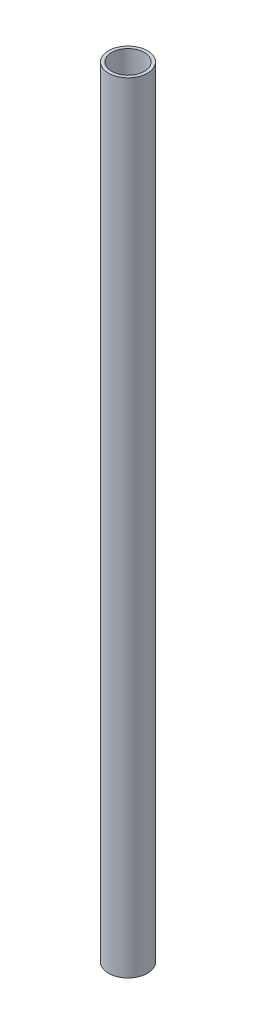
SolidWorks part; units mm, degrees
ref_plane "Front Plane" through (0, 0, 0) normal (0, 0, 1) x (1, 0, 0)
ref_plane "Top Plane" through (0, 0, 0) normal (0, 1, 0) x (1, 0, 0)
ref_plane "Right Plane" through (0, 0, 0) normal (1, 0, 0) x (0, 0, -1)
sketch "Sketch1" plane through (0, 0, 0) normal (0, 1, 0) x (1, 0, 0)
  circle A0 centre (0, 0) radius 12.5
  circle A1 centre (0, 0) radius 10.5
  dimension "D1" = 25
  dimension "D2" = 21
extrude "Boss-Extrude1" add sketch "Sketch1" along normal blind 500
equation "\"D1@Sketch1\" = \"cf_tube_outer_diameter\""
equation "\"D1@Boss-Extrude1\"= \"mid_tube_length\""
equation "\"cf_tube_outer_diameter\"= 25mm"
equation "\"mid_plate_mid_to_top\" = 100mm"
equation "\"mid_plate_mid_to_bottom\" = 30mm"
equation "\"mid_plate_horizontal_spacing\"=250mm"
equation "\"mid_tube_length\" = 500mm"
equation "\"cf_tube_inner_diameter\" = 21mm"
equation "\"D2@Sketch1\"=\"cf_tube_inner_diameter\""
